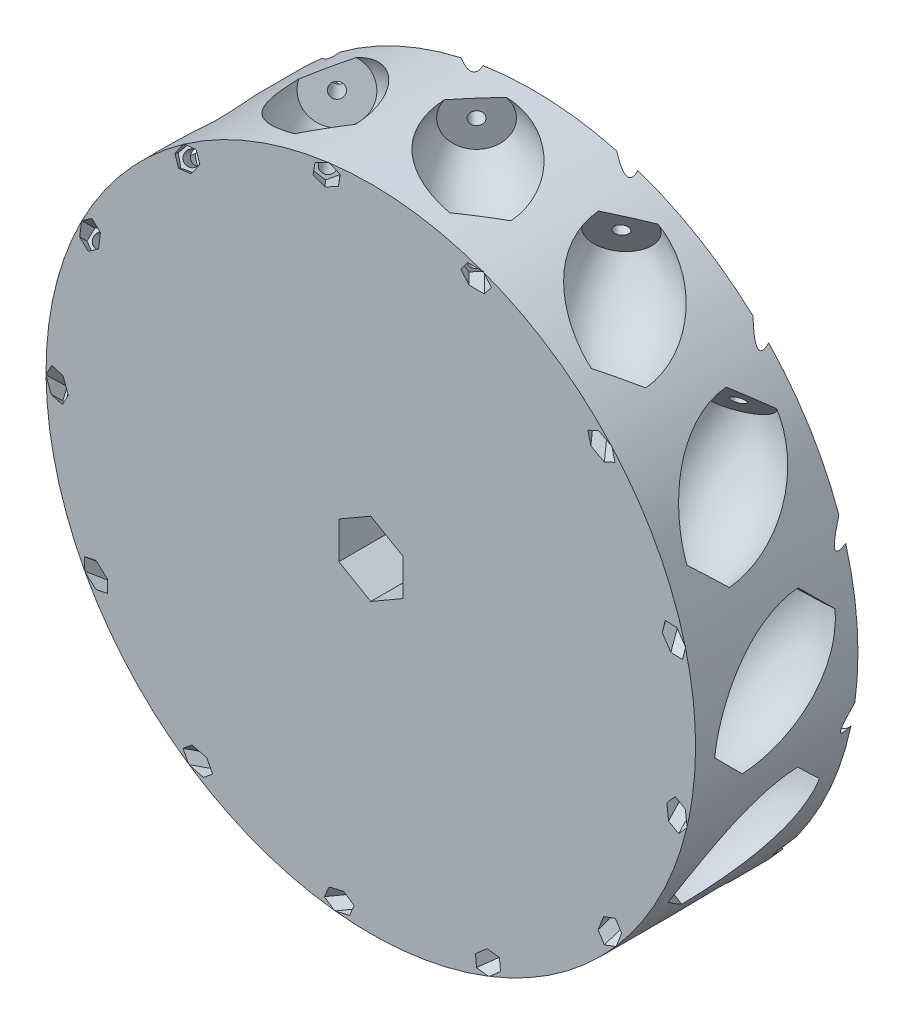
SolidWorks part; units mm, degrees
ref_plane "Front Plane" through (0, 0, 0) normal (0, 0, 1) x (1, 0, 0)
ref_plane "Top Plane" through (0, 0, 0) normal (0, 1, 0) x (1, 0, 0)
ref_plane "Right Plane" through (0, 0, 0) normal (1, 0, 0) x (0, 0, -1)
sketch "Sketch1" plane through (0, 0, 0) normal (0, 0, 1) x (1, 0, 0)
  line L1 (0, 8.6603) -> (-7.5, 4.3301)
  line L2 (-7.5, 4.3301) -> (-7.5, -4.3301)
  line L3 (-7.5, -4.3301) -> (0, -8.6603)
  line L4 (0, -8.6603) -> (7.5, -4.3301)
  line L5 (7.5, -4.3301) -> (7.5, 4.3301)
  line L6 (7.5, 4.3301) -> (0, 8.6603)
  circle A0 centre (0, 0) radius 76.2
  circle A1 centre (0, 0) radius 7.5 construction
  dimension "D1" = 152.4
  dimension "D2" = 15
extrude "Boss-Extrude1" add sketch "Sketch1" along normal blind 38.1
ref_plane "Plane1" through (65.9911, 38.1, 0) normal (0.866, 0.5, 0) x (0, 0, -1)
ref_plane "Plane2" through (61.5917, 35.56, 0) normal (0.866, 0.5, 0) x (0, 0, -1)
sketch "Sketch2" plane through (61.5917, 35.56, 0) normal (0.866, 0.5, 0) x (0, 0, -1)
  line L0 (0, -19.05) -> (-38.1, 19.05) construction
  line L1 (-38.1, 76.2) -> (-38.1, -76.2) construction
  line L2 (-38.1, 19.05) -> (0, 19.05) construction
  line L3 (0, -76.2) -> (0, 76.2) construction
  line L5 (-13.6618, -12.5724) -> (-6.4776, -5.3882) construction
  line L7 (-31.6224, 5.3882) -> (-24.4382, 12.5724) construction
  line L9 (-13.6618, -12.5724) -> (-24.4382, 12.5724) construction
  line L10 (-31.6224, 5.3882) -> (-6.4776, -5.3882) construction
  line L14 (-30.1516, 11.1016) -> (-7.9484, -11.1016)
  line L15 (-34.8334, 6.4198) -> (-25.4698, 15.7834)
  line L16 (-12.6302, -15.7834) -> (-3.2666, -6.4198)
  arc A0 (-24.4382, 12.5724) -> (-6.4776, -5.3882) centre (-28.8983, -9.8483) cw construction
  arc A1 (-31.6224, 5.3882) -> (-13.6618, -12.5724) centre (-9.2017, 9.8483) ccw construction
  arc A2 (-25.4698, 15.7834) -> (-3.2666, -6.4198) centre (-28.8983, -9.8483) cw
  arc A3 (-34.8334, 6.4198) -> (-12.6302, -15.7834) centre (-9.2017, 9.8483) ccw
  point P10 (-19.05, 0)
  point P11 (-19.05, 0)
  point P22 (-10.0697, -8.9803)
  dimension "D5" = 22.86
  dimension "D1" = 45
  dimension "D2" = 25.4
  dimension "D3" = 10.16
  dimension "D4" = 3
revolve "Cut-Revolve1" cut sketch "Sketch2" angle 360 about L14 region at (59.7395, 38.7682, 15.3455)
sketch "Sketch4" plane through (-10.3133, 17.8631, 20.6266) normal (0.3536, -0.6124, -0.7071) x (-0.9354, -0.2315, -0.2673)
  line L0 (-77.0391, 11.8433) -> (-72.1462, 20.9192)
  line L1 (-68.3957, 14.4837) -> (-69.7298, 16.6464)
  line L2 (-69.7298, 16.6464) -> (-72.2698, 16.5724)
  line L3 (-72.2698, 16.5724) -> (-73.4757, 14.3356)
  line L4 (-73.4757, 14.3356) -> (-72.1415, 12.1729)
  line L5 (-72.1415, 12.1729) -> (-69.6015, 12.247)
  line L6 (-69.6015, 12.247) -> (-68.3957, 14.4837)
  circle A1 centre (-70.9357, 14.4097) radius 1.585
  arc A2 (-77.0391, 11.8433) -> (-72.1462, 20.9192) centre (-70.9357, 14.4097) ccw construction
  circle A3 centre (-70.9357, 14.4097) radius 3.1
  circle A4 centre (-70.9357, 14.4097) radius 2.2006 construction
  ellipse E1 centre (-11.0254, -27.0065) end of major axis (29.7052, 72.7627) minor radius 76.2 (-72.1462, 20.9192) -> (-77.0391, 11.8433) ccw construction
  point P12 (-70.9357, 14.4097)
  dimension "D1" = 3.17
  dimension "D2" = 6.2
  dimension "D3" = 5.08
extrude "Cut-Extrude1" cut sketch "Sketch4" against normal through all both and the other way through all contours A1
extrude "Cut-Extrude2" cut sketch "Sketch4<4>" along normal blind 7.62 from offset 15.24 contours A3 L6 L5 L4 L3 L2 L1 | L5 L6 L1 L2 L3 L4 A1 region at (54.2847, 43.9746, 30.3124) region at (58.8587, 45.8715, 30.9567) offset against normal yes
sketch "Sketch4<4>" plane through (-10.3133, 17.8631, 20.6266) normal (0.3536, -0.6124, -0.7071) x (-0.9354, -0.2315, -0.2673) same geometry as "Sketch4"
extrude "Cut-Extrude3" cut sketch "Sketch4<5>" against normal blind 7.62 from offset 45.72 contours L5 L6 L1 L2 L3 L4 A1 region at (54.2847, 43.9746, 30.3124)
sketch "Sketch4<5>" plane through (-10.3133, 17.8631, 20.6266) normal (0.3536, -0.6124, -0.7071) x (-0.9354, -0.2315, -0.2673) same geometry as "Sketch4"
pattern_circular "CirPattern1" count 13 over 360 about axis through (0, 0, 0) along (0, 0, 1) of "Cut-Revolve1", "Cut-Extrude1", "Cut-Extrude2", "Cut-Extrude3"
ref_plane "Plane3" through (0, 0, 63.5) normal (0, 0, 1) x (1, 0, 0)
sketch "Sketch5" plane through (0, 0, 38.1) normal (0, 0, 1) x (1, 0, 0)
  circle A0 centre (0, 0) radius 19.05
  dimension "D1" = 38.1
extrude "Boss-Extrude2" add sketch "Sketch5" along normal blind 50.8
mirror "Mirror2" about plane through (0, 0, 63.5) normal (0, 0, 1) of "Boss-Extrude2", "CirPattern1", "Cut-Extrude3", "Cut-Extrude2", "Cut-Extrude1", "Cut-Revolve1", "Boss-Extrude1"
sketch "Sketch6" plane through (0, 0, 0) normal (0, 0, -1) x (-1, 0, 0)
  circle A0 centre (0, 0) radius 88.9
  dimension "D1" = 177.8
extrude "Cut-Extrude4" cut sketch "Sketch6" against normal up to surface (88.9 mm away) up to face at (0, 0, 88.9)
